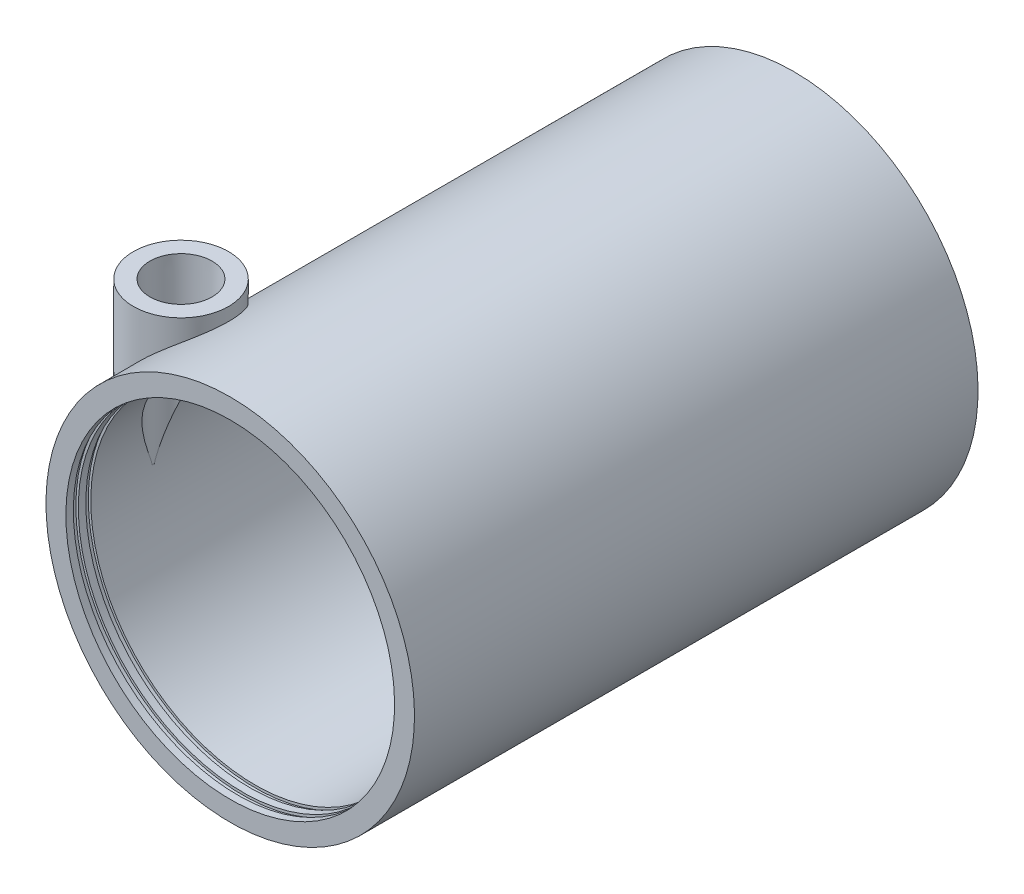
SolidWorks part; units mm, degrees
material "Alloy Steel"
ref_plane "Front Plane" through (0, 0, 0) normal (0, 0, 1) x (1, 0, 0)
ref_plane "Top Plane" through (0, 0, 0) normal (0, 1, 0) x (1, 0, 0)
ref_plane "Right Plane" through (0, 0, 0) normal (1, 0, 0) x (0, 0, -1)
ref_axis "CENTER" through (0, 0, 55) along (0, 0, -1)
sketch "Sketch1" plane through (0, 0, 0) normal (1, 0, 0) x (0, 0, -1)
  line L0 (0, 33) -> (109.1612, 33)
  line L1 (109.1612, 33) -> (109.1612, 12.4867)
  line L3 (113.1612, 13.5585) -> (113.1612, 37)
  line L4 (113.1612, 37) -> (0, 37)
  line L5 (0, 37) -> (0, 33)
  line L6 (109.1612, 12.4867) -> (113.1612, 13.5585)
  line L7 (1.7895, 0) -> (-49998.2105, 0) construction
  line L8 (-55, 0) -> (55, 0) construction
  dimension "D1" = 4
  dimension "D2" = 4
  dimension "D3" = 66
  dimension "D4" = 109.1612
  dimension "D5" = 24.9734
  dimension "D6" = 15
revolve "Main Base" add sketch "Sketch1" angle 360 about L7
sketch "Sketch2" plane through (0, 0, 0) normal (1, 0, 0) x (0, 0, -1)
  line L0 (109.1612, 33) -> (0, 33) construction
  line L1 (1.5, 33) -> (2.5, 33)
  line L2 (1.5, 33) -> (1.5, 33.5)
  line L3 (1.5, 33.5) -> (2.5, 33.5)
  line L4 (2.5, 33) -> (2.5, 33.5)
  line L5 (0, 37) -> (0, -37) construction
  line L7 (4, 33) -> (5, 33)
  line L8 (4, 33) -> (4, 33.5)
  line L9 (4, 33.5) -> (5, 33.5)
  line L10 (5, 33) -> (5, 33.5)
  dimension "D1" = 0.5
  dimension "D2" = 1
  dimension "D3" = 1.5
  dimension "D4" = 1.5
revolve "Radial O-Ring" cut sketch "Sketch2" angle 360 about axis through (0, 0, 55) along (0, 0, -1)
sketch "Sketch3" plane through (0, 0, 0) normal (0, 1, 0) x (1, 0, 0)
  line L0 (-24.6457, 8) -> (-50024.6457, 8) construction
  line L1 (-37, 0) -> (37, 0) construction
  line L2 (-37, 113.1612) -> (-37, 0) construction
  circle A0 centre (-27.4437, 17.5563) radius 5.5562 construction
  circle A1 centre (-27.4437, 17.5563) radius 9.5562
  dimension "D2" = 11.1125
  dimension "D3" = 4
  dimension "D1" = 8
extrude "Weld Bungs Inlet" add sketch "Sketch3" along normal up to surface (10.1839 mm away) from offset 35
sketch "Sketch6" plane through (0, 0, 0) normal (0, 1, 0) x (1, 0, 0)
  line L0 (-37, 113.1612) -> (-37, 17.5562) construction
  line L1 (-27.4437, 107.1612) -> (49972.5562, 107.1612) construction
  line L2 (37, 113.1612) -> (-37, 113.1612) construction
  circle A0 centre (-27.4437, 97.605) radius 9.5562
  circle A1 centre (-27.4437, 17.5563) radius 9.5562 construction
  dimension "D1" = 6
extrude "Weld Bungs Outlet" add sketch "Sketch6" along normal up to surface (10.1839 mm away) from offset 35 offset against normal yes
hole_wizard "1/4 NPT Tapped Hole1" positions "Sketch4" profile "Sketch5" size "1/4" standard "ANSI Inch"
sketch "Sketch4" plane through (0, 35, 0) normal (0, 1, 0) x (1, 0, 0)
  point P0 (-27.4437, 17.5563)
  point P9 (-27.4437, 97.605)
  point P11 (0, 0)
cosmetic thread "Hole Thread2" parameters "D1"=10.02, "D2"=13.7154
sketch "Sketch5" plane through (-27.4437, 35, -17.5563) normal (1, 0, 0) x (0, 0, 1)
  line L0 (0, 0) -> (0, 38.3413)
  line L1 (5.5626, 34.999) -> (0, 38.3413)
  line L2 (-5.5626, 34.999) -> (0, 38.3413) construction
  line L3 (5.5626, 34.999) -> (5.5626, 10.02)
  line L4 (5.5626, 10.02) -> (5.9437, 10.02)
  line L5 (5.9437, 10.02) -> (6.2437, 0)
  line L6 (-5.9437, 10.02) -> (-6.2437, 0) construction
  line L7 (6.2437, 0) -> (0, 0)
  line L8 (0, -6.35) -> (0, 107.95) construction
  line L11 (-5.5626, 10.02) -> (-5.9437, 10.02) construction
  dimension "Tap Drill Dia." = 11.1252
  dimension "Tap Drill Depth" = 34.999
  dimension "Thread Dia." = 12.4874
  dimension "Thread Angle" = 3.43
  dimension "Thread Depth" = 10.02
  dimension "Drill Angle" = 118
hole_wizard "1/4 NPT Tapped Hole2" positions "Sketch7" profile "Sketch8" size "1/4" standard "ANSI Inch"
sketch "Sketch7" plane through (0, -35, 0) normal (0, -1, 0) x (-1, 0, 0)
  point P0 (27.4437, 97.605)
sketch "Sketch8" plane through (-27.4437, -35, -97.605) normal (1, 0, 0) x (0, 0, -1)
  line L0 (0, 0) -> (0, 38.3413)
  line L1 (5.5626, 34.999) -> (0, 38.3413)
  line L2 (-5.5626, 34.999) -> (0, 38.3413) construction
  line L3 (5.5626, 34.999) -> (5.5626, 10.02)
  line L4 (5.5626, 10.02) -> (5.9437, 10.02)
  line L5 (5.9437, 10.02) -> (6.2437, 0)
  line L6 (-5.9437, 10.02) -> (-6.2437, 0) construction
  line L7 (6.2437, 0) -> (0, 0)
  line L8 (0, -6.35) -> (0, 107.95) construction
  line L11 (-5.5626, 10.02) -> (-5.9437, 10.02) construction
  dimension "Tap Drill Dia." = 11.1252
  dimension "Tap Drill Depth" = 34.999
  dimension "Thread Dia." = 12.4874
  dimension "Thread Angle" = 3.43
  dimension "Thread Depth" = 10.02
  dimension "Drill Angle" = 118
cosmetic thread "Hole Thread3" parameters "D1"=10.02, "D2"=13.716
